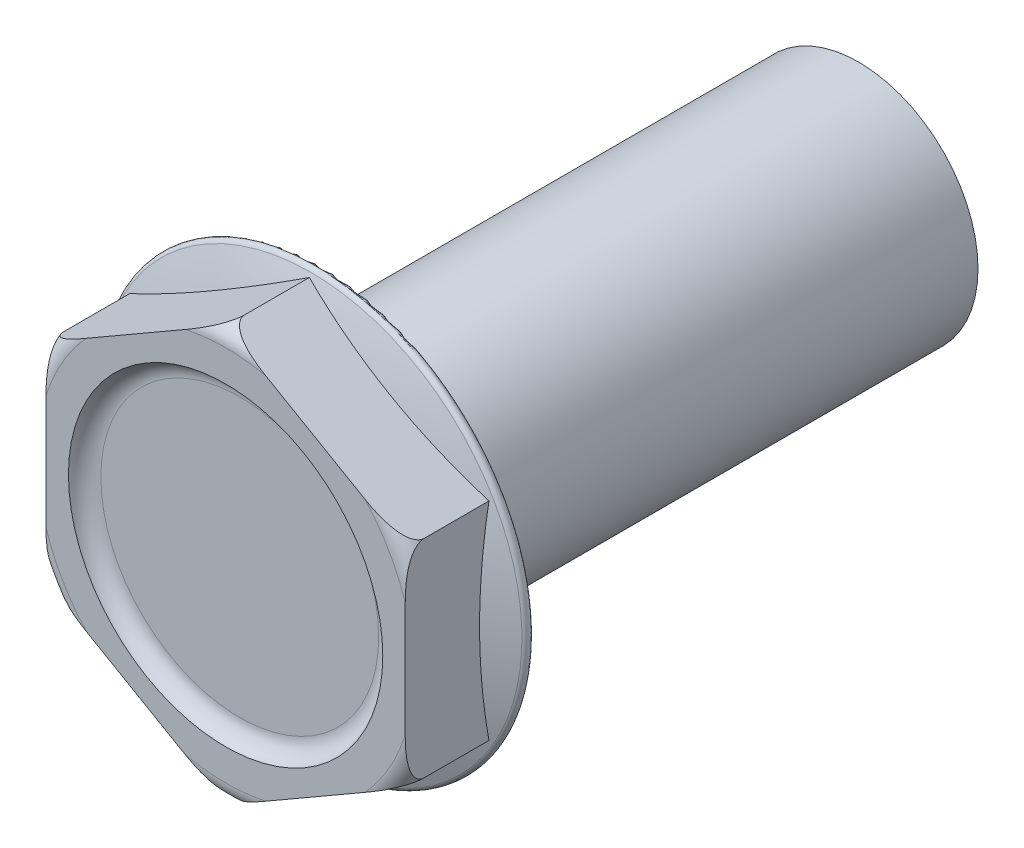
SolidWorks part; units mm, degrees
note: '?' marks a value the reader was unsure of.
extrude "Shank" add sketch "Shank Sketch" against normal blind 57.15
sketch "Shank Sketch" plane through (0, 0, 0) normal (0, 0, 1) x (1, 0, 0)
  line L0 (50, 0) -> (-50, 0) construction
  line L1 (0, -50) -> (0, 50) construction
  circle A0 centre (0, 0) radius 12.7
  dimension "Shank diameter" = 25.4
extrude "Head" add sketch "Head Sketch" along normal blind 10
sketch "Head Sketch" plane through (0, 0, 0) normal (0, 0, 1) x (1, 0, 0)
  line L0 (0, 21.997) -> (19.05, 10.9985)
  line L1 (19.05, 10.9985) -> (19.05, -10.9985)
  line L2 (19.05, -10.9985) -> (0, -21.997)
  line L3 (0, -21.997) -> (-19.05, -10.9985)
  line L4 (-19.05, -10.9985) -> (-19.05, 10.9985)
  line L5 (-19.05, 10.9985) -> (0, 21.997)
  line L6 (19.05, 10.9985) -> (-19.05, -10.9985) construction
  line L7 (0, 21.997) -> (0, -21.997) construction
  line L8 (-19.05, 10.9985) -> (19.05, -10.9985) construction
  point P0 (0, 0)
  dimension "D1" = 60
  dimension "D2" = 60
  dimension "Width across flats" = 38.1
ref_plane "Plane1" through (0, 0, 0) normal (0, 0, 1) x (1, 0, 0)
ref_plane "Plane2" through (0, 0, 0) normal (0, 1, 0) x (-1, 0, 0)
ref_plane "Plane3" through (0, 0, 0) normal (1, 0, 0) x (0, 0, -1)
other "Configuration Table"
sketch "Sketch3" plane through (0, 0, 0) normal (0, 1, 0) x (-1, 0, 0)
  line L0 (0, 0) -> (0, 10) construction
  line L1 (0, -57.15) -> (0, 0) construction
  line L4 (-22.225, 0) -> (0, 0)
  line L5 (0, 0) -> (0, 5)
  arc A0 (0, 5) -> (-22.3993, 0.9686) centre (0, -59.2438) ccw
  arc A1 (-22.225, 0) -> (-22.3993, 0.9686) centre (-22.225, 0.5) cw
  dimension "D1" = 0.5
  dimension "D2" = 44.45
  dimension "D3" = 5
revolve "Flange" add sketch "Sketch3" angle 360 about L0
ref_axis "Axis1" through (0, 0, -107.15) along (0, 0, 1)?
sketch "Sketch5" plane through (0, 0, 0) normal (1, 0, 0) x (0, 0, -1)
  line L0 (-10, -19.997) -> (-10, -21.997)
  line L1 (-10, -21.997) -> (-8, -21.997)
  line L2 (-10, -21.997) -> (-1.1168, -21.997) construction
  line L3 (-10, -21.997) -> (-10, -10.9985) construction
  line L5 (-15.0856, 0) -> (-8.1394, 0) construction
  line L6 (50, 0) -> (-50, 0) construction
  arc A0 (-10, -19.997) -> (-8, -21.997) centre (-8, -19.997) ccw
  dimension "D1" = 2
revolve "Head Trim" cut sketch "Sketch5" angle 360 about L5
sketch "Sketch6" plane through (0, 0, 10) normal (0, 0, 1) x (1, 0, 0)
  circle A3 centre (0, 0) radius 16.6687
  dimension "D1" = 33.3375
extrude "Head Cut" cut sketch "Sketch6" against normal blind 1.5
fillet "Fillet1" radius 2 1 edges at (16.6687, 0, 8.5)
fillet "Fillet2" radius 0.5 1 edges at (12.7, 0, 0)
sketch "Thread End" plane through (0, 0, 0) normal (1, 0, 0) x (0, 0, -1)
  line L0 (6.35, 12.7) -> (6.35, 12.65)
  line L1 (57.15, 12.7) -> (0.5, 12.7) construction
  line L2 (6.35, 12.65) -> (57.15, 12.65)
  line L3 (57.15, 12.7) -> (6.35, 12.7)
  line L4 (21.5519, 0) -> (27.4271, 0) construction
  line L5 (57.15, 0) -> (0.5, 0) construction
  line L6 (57.15, -12.7) -> (57.15, 12.7) construction
  line L7 (57.15, 12.65) -> (57.15, 12.7)
  dimension "D1" = 0.05
  dimension "Length of thread" = 50.8
revolve "Thread Cut" cut sketch "Thread End" angle 360 about L4
cosmetic thread "Cosmetic Thread2" parameters "D2"=11
equation "\"D1@Sketch6\" = \"Width across flats@Head Sketch\"*7/8"
